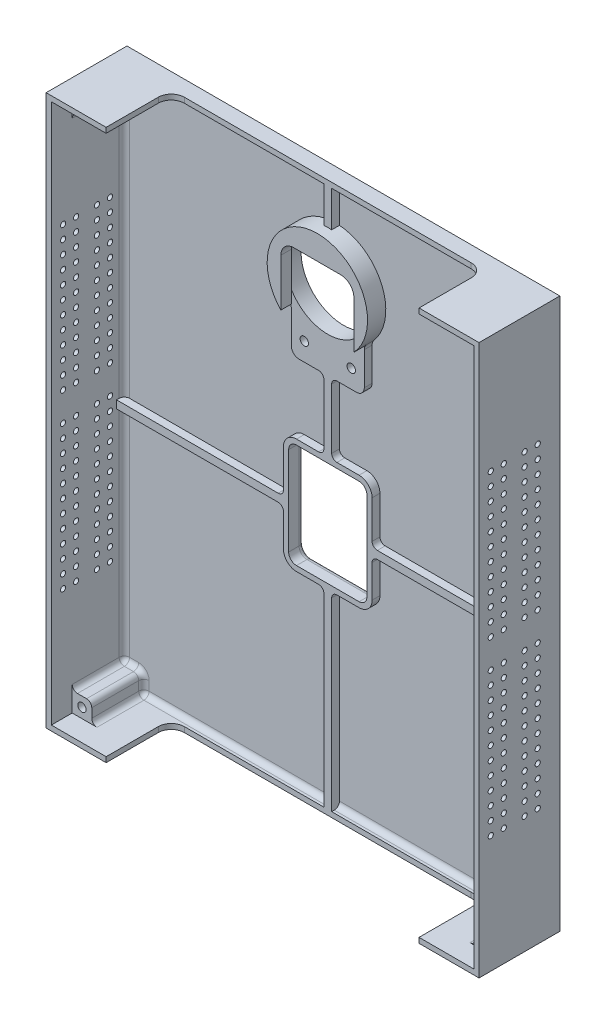
SolidWorks part; units mm, degrees
ref_plane "Front Plane" through (0, 0, 0) normal (0, 0, 1) x (1, 0, 0)
ref_plane "Top Plane" through (0, 0, 0) normal (0, 1, 0) x (1, 0, 0)
ref_plane "Right Plane" through (0, 0, 0) normal (1, 0, 0) x (0, 0, -1)
ref_plane "Plane1" through (0, 0, -1) normal (0, 0, 1) x (1, 0, 0)
sketch "Sketch5" plane through (0, 0, -1) normal (0, 0, 1) x (1, 0, 0)
  line L0 (100, 83.2573) -> (100, -169.2647) construction
  line L2 (17, 83.2573) -> (17, -127.7573)
  line L3 (17, -127.7573) -> (183, -127.7573)
  line L4 (183, 83.2573) -> (183, -127.7573)
  line L5 (17, 83.2573) -> (183, 83.2573)
  circle A0 centre (100, 48.2573) radius 16.25
  point P17 (45, 83.2573)
  dimension "D1" = 166
  dimension "D2" = 83
extrude "Boss-Extrude5" add sketch "Sketch5" along normal blind 3
sketch "Sketch6" plane through (0, 0, 2) normal (0, 0, 1) x (1, 0, 0)
  line L0 (116.25, 48.2573) -> (83.75, 48.2573) construction
  line L2 (86, 35.0451) -> (86, 18.2573)
  line L3 (86, 18.2573) -> (114, 18.2573)
  line L4 (114, 35.0451) -> (114, 18.2573)
  line L5 (100, 48.2573) -> (100, 52.872) construction
  circle A1 centre (100, 48.2573) radius 16.25
  arc A2 (114, 35.0451) -> (86, 35.0451) centre (100, 48.2573) ccw
  circle A6 centre (100, 48.2573) radius 16.25 construction
extrude "Boss-Extrude6" add sketch "Sketch6" along normal blind 3
sketch "Sketch7" plane through (0, 0, 5) normal (0, 0, 1) x (1, 0, 0)
  line L0 (114, 35.0451) -> (114, 53.2573)
  line L1 (109, 58.2573) -> (91, 58.2573)
  line L2 (86, 53.2573) -> (86, 35.0451)
  line L3 (100, 64.5073) -> (100, 48.2573) construction
  line L4 (100, 48.2573) -> (116.25, 48.2573) construction
  arc A4 (91, 58.2573) -> (86, 53.2573) centre (91, 53.2573) ccw
  arc A5 (114, 53.2573) -> (109, 58.2573) centre (109, 53.2573) ccw
  arc A8 (114, 35.0451) -> (86, 35.0451) centre (100, 48.2573) ccw
  circle A9 centre (100, 48.2573) radius 19.25 construction
  circle A10 centre (100, 48.2573) radius 16.25 construction
extrude "Boss-Extrude7" add sketch "Sketch7" along normal blind 4
sketch "Sketch8" plane through (0, 0, 2) normal (0, 0, 1) x (1, 0, 0)
  line L4 (17, -127.7573) -> (183, -127.7573)
  line L5 (183, -127.7573) -> (183, 83.2573)
  line L6 (183, 83.2573) -> (17, 83.2573)
  line L7 (17, 83.2573) -> (17, -127.7573)
  line L8 (17, -127.7573) -> (183, -127.7573)
  line L9 (183, -127.7573) -> (183, 83.2573)
  line L10 (183, 83.2573) -> (17, 83.2573)
  line L11 (17, 83.2573) -> (17, -127.7573)
  line L12 (19, -125.7573) -> (181, -125.7573)
  line L13 (181, -125.7573) -> (181, 81.2573)
  line L14 (181, 81.2573) -> (19, 81.2573)
  line L15 (19, 81.2573) -> (19, -125.7573)
  dimension "D1" = 0
  dimension "D2" = 2
extrude "Boss-Extrude8" add sketch "Sketch8" along normal blind 28
fillet "Fillet2" radius 3 4 edges at (114, 18.2573, 3.5) (114, 35.0451, 3.5) (86, 18.2573, 3.5) (86, 35.0451, 3.5)
sketch "Sketch9" plane through (0, 0, 5) normal (0, 0, 1) x (1, 0, 0)
  line L0 (100, 48.2573) -> (100, 25.2573) construction
  line L1 (91, 25.2573) -> (109, 25.2573) construction
  line L2 (100, 25.2573) -> (100, 23.2329) construction
  circle A0 centre (91, 25.2573) radius 1.6
  circle A1 centre (109, 25.2573) radius 1.6
extrude "Cut-Extrude1" cut sketch "Sketch9" against normal up to surface (6 mm away) up to face at (100, -22.25, -1)
sketch "Sketch12" plane through (183, 0, 0) normal (1, 0, 0) x (0, 0, -1)
  circle A0 centre (-12.5, -16.7427) radius 1
  circle A1 centre (-7.5, -16.7427) radius 1
  circle A2 centre (-7.5, -11.7427) radius 1
  circle A3 centre (-7.5, -6.7427) radius 1
  circle A4 centre (-7.5, -1.7427) radius 1
  circle A5 centre (-7.5, 3.2573) radius 1
  circle A6 centre (-7.5, 8.2573) radius 1
  circle A7 centre (-7.5, 13.2573) radius 1
  circle A8 centre (-7.5, 18.2573) radius 1
  circle A9 centre (-7.5, 23.2573) radius 1
  circle A10 centre (-7.5, 28.2573) radius 1
  circle A11 centre (-7.5, 33.2573) radius 1
  circle A12 centre (-7.5, 38.2573) radius 1
  circle A13 centre (-12.5, -11.7427) radius 1
  circle A14 centre (-12.5, -6.7427) radius 1
  circle A15 centre (-12.5, -1.7427) radius 1
  circle A16 centre (-12.5, 3.2573) radius 1
  circle A17 centre (-12.5, 8.2573) radius 1
  circle A18 centre (-12.5, 13.2573) radius 1
  circle A19 centre (-12.5, 18.2573) radius 1
  circle A20 centre (-12.5, 23.2573) radius 1
  circle A21 centre (-12.5, 28.2573) radius 1
  circle A22 centre (-12.5, 33.2573) radius 1
  circle A23 centre (-12.5, 38.2573) radius 1
  circle A24 centre (-12.5, -82.7573) radius 1
  circle A25 centre (-12.5, -77.7573) radius 1
  circle A26 centre (-12.5, -72.7573) radius 1
  circle A27 centre (-12.5, -67.7573) radius 1
  circle A28 centre (-12.5, -62.7573) radius 1
  circle A29 centre (-12.5, -57.7573) radius 1
  circle A30 centre (-12.5, -52.7573) radius 1
  circle A31 centre (-12.5, -47.7573) radius 1
  circle A32 centre (-12.5, -42.7573) radius 1
  circle A33 centre (-12.5, -37.7573) radius 1
  circle A34 centre (-12.5, -32.7573) radius 1
  circle A35 centre (-7.5, -82.7573) radius 1
  circle A36 centre (-7.5, -77.7573) radius 1
  circle A37 centre (-7.5, -72.7573) radius 1
  circle A38 centre (-7.5, -67.7573) radius 1
  circle A39 centre (-7.5, -62.7573) radius 1
  circle A40 centre (-7.5, -57.7573) radius 1
  circle A41 centre (-7.5, -52.7573) radius 1
  circle A42 centre (-7.5, -47.7573) radius 1
  circle A43 centre (-7.5, -42.7573) radius 1
  circle A44 centre (-7.5, -37.7573) radius 1
  circle A45 centre (-7.5, -32.7573) radius 1
  circle A46 centre (-7.5, -27.7573) radius 1
  circle A47 centre (-12.5, -27.7573) radius 1
  circle A48 centre (-20.5, -27.7573) radius 1
  circle A49 centre (-25.5, -27.7573) radius 1
  circle A50 centre (-25.5, -32.7573) radius 1
  circle A51 centre (-25.5, -37.7573) radius 1
  circle A52 centre (-25.5, -42.7573) radius 1
  circle A53 centre (-25.5, -47.7573) radius 1
  circle A54 centre (-25.5, -52.7573) radius 1
  circle A55 centre (-25.5, -57.7573) radius 1
  circle A56 centre (-25.5, -62.7573) radius 1
  circle A57 centre (-25.5, -67.7573) radius 1
  circle A58 centre (-25.5, -72.7573) radius 1
  circle A59 centre (-25.5, -77.7573) radius 1
  circle A60 centre (-25.5, -82.7573) radius 1
  circle A61 centre (-20.5, -32.7573) radius 1
  circle A62 centre (-20.5, -37.7573) radius 1
  circle A63 centre (-20.5, -42.7573) radius 1
  circle A64 centre (-20.5, -47.7573) radius 1
  circle A65 centre (-20.5, -52.7573) radius 1
  circle A66 centre (-20.5, -57.7573) radius 1
  circle A67 centre (-20.5, -62.7573) radius 1
  circle A68 centre (-20.5, -67.7573) radius 1
  circle A69 centre (-20.5, -72.7573) radius 1
  circle A70 centre (-20.5, -77.7573) radius 1
  circle A71 centre (-20.5, -82.7573) radius 1
  circle A72 centre (-20.5, 38.2573) radius 1
  circle A73 centre (-20.5, 33.2573) radius 1
  circle A74 centre (-20.5, 28.2573) radius 1
  circle A75 centre (-20.5, 23.2573) radius 1
  circle A76 centre (-20.5, 18.2573) radius 1
  circle A77 centre (-20.5, 13.2573) radius 1
  circle A78 centre (-20.5, 8.2573) radius 1
  circle A79 centre (-20.5, 3.2573) radius 1
  circle A80 centre (-20.5, -1.7427) radius 1
  circle A81 centre (-20.5, -6.7427) radius 1
  circle A82 centre (-20.5, -11.7427) radius 1
  circle A83 centre (-25.5, 38.2573) radius 1
  circle A84 centre (-25.5, 33.2573) radius 1
  circle A85 centre (-25.5, 28.2573) radius 1
  circle A86 centre (-25.5, 23.2573) radius 1
  circle A87 centre (-25.5, 18.2573) radius 1
  circle A88 centre (-25.5, 13.2573) radius 1
  circle A89 centre (-25.5, 8.2573) radius 1
  circle A90 centre (-25.5, 3.2573) radius 1
  circle A91 centre (-25.5, -1.7427) radius 1
  circle A92 centre (-25.5, -6.7427) radius 1
  circle A93 centre (-25.5, -11.7427) radius 1
  circle A94 centre (-25.5, -16.7427) radius 1
  circle A95 centre (-20.5, -16.7427) radius 1
  dimension "D1" = 2
  dimension "D2" = 12
extrude "Cut-Extrude4" cut sketch "Sketch12" against normal up to surface (2 mm away) up to face at (181, -22.25, 16)
sketch "Sketch13" plane through (0, 0, -1) normal (0, 0, -1) x (-1, 0, 0)
  line L0 (-183, -30.7808) -> (-100, -30.7808) construction
  line L1 (-183, -127.7573) -> (-183, 83.2573) construction
  line L6 (-100, 83.2573) -> (-100, -30.7808) construction
  line L7 (-183, 83.2573) -> (-17, 83.2573) construction
  line L14 (-85, -47.7808) -> (-85, -13.7808)
  line L15 (-88, -10.7808) -> (-112, -10.7808)
  line L16 (-115, -13.7808) -> (-115, -47.7808)
  line L17 (-112, -50.7808) -> (-88, -50.7808)
  circle A1 centre (-100, -30.7808) radius 9 construction
  arc A15 (-88, -50.7808) -> (-85, -47.7808) centre (-88, -47.7808) ccw
  arc A16 (-85, -13.7808) -> (-88, -10.7808) centre (-88, -13.7808) ccw
  arc A17 (-112, -10.7808) -> (-115, -13.7808) centre (-112, -13.7808) ccw
  arc A18 (-115, -47.7808) -> (-112, -50.7808) centre (-112, -47.7808) ccw
extrude "Cut-Extrude5" cut sketch "Sketch13" against normal blind 3
sketch "Sketch14" plane through (17, 0, 0) normal (-1, 0, 0) x (0, 0, 1)
  circle A1 centre (12.5, -82.7573) radius 1
  circle A2 centre (12.5, -82.7573) radius 1
  circle A3 centre (12.5, -16.7427) radius 1
  circle A4 centre (12.5, -16.7427) radius 1
  circle A5 centre (7.5, 18.2573) radius 1
  circle A6 centre (7.5, 18.2573) radius 1
  circle A7 centre (7.5, 13.2573) radius 1
  circle A8 centre (7.5, 13.2573) radius 1
  circle A9 centre (7.5, 8.2573) radius 1
  circle A10 centre (7.5, 8.2573) radius 1
  circle A11 centre (7.5, 3.2573) radius 1
  circle A12 centre (7.5, 3.2573) radius 1
  circle A13 centre (7.5, -1.7427) radius 1
  circle A14 centre (7.5, -1.7427) radius 1
  circle A15 centre (7.5, -6.7427) radius 1
  circle A16 centre (7.5, -6.7427) radius 1
  circle A17 centre (7.5, -11.7427) radius 1
  circle A18 centre (7.5, -11.7427) radius 1
  circle A19 centre (7.5, -16.7427) radius 1
  circle A20 centre (7.5, -16.7427) radius 1
  circle A21 centre (12.5, 3.2573) radius 1
  circle A22 centre (12.5, 3.2573) radius 1
  circle A23 centre (12.5, -1.7427) radius 1
  circle A24 centre (12.5, -1.7427) radius 1
  circle A25 centre (12.5, -6.7427) radius 1
  circle A26 centre (12.5, -6.7427) radius 1
  circle A27 centre (12.5, -11.7427) radius 1
  circle A28 centre (12.5, -11.7427) radius 1
  circle A29 centre (7.5, 38.2573) radius 1
  circle A30 centre (7.5, 38.2573) radius 1
  circle A31 centre (7.5, 33.2573) radius 1
  circle A32 centre (7.5, 33.2573) radius 1
  circle A33 centre (7.5, 28.2573) radius 1
  circle A34 centre (7.5, 28.2573) radius 1
  circle A35 centre (7.5, 23.2573) radius 1
  circle A36 centre (7.5, 23.2573) radius 1
  circle A37 centre (12.5, -77.7573) radius 1
  circle A38 centre (12.5, -77.7573) radius 1
  circle A39 centre (12.5, 38.2573) radius 1
  circle A40 centre (12.5, 38.2573) radius 1
  circle A41 centre (12.5, 33.2573) radius 1
  circle A42 centre (12.5, 33.2573) radius 1
  circle A43 centre (12.5, 28.2573) radius 1
  circle A44 centre (12.5, 28.2573) radius 1
  circle A45 centre (12.5, 23.2573) radius 1
  circle A46 centre (12.5, 23.2573) radius 1
  circle A47 centre (12.5, 18.2573) radius 1
  circle A48 centre (12.5, 18.2573) radius 1
  circle A49 centre (12.5, 13.2573) radius 1
  circle A50 centre (12.5, 13.2573) radius 1
  circle A51 centre (12.5, 8.2573) radius 1
  circle A52 centre (12.5, 8.2573) radius 1
  circle A53 centre (12.5, -37.7573) radius 1
  circle A54 centre (12.5, -37.7573) radius 1
  circle A55 centre (12.5, -42.7573) radius 1
  circle A56 centre (12.5, -42.7573) radius 1
  circle A57 centre (12.5, -47.7573) radius 1
  circle A58 centre (12.5, -47.7573) radius 1
  circle A59 centre (12.5, -52.7573) radius 1
  circle A60 centre (12.5, -52.7573) radius 1
  circle A61 centre (12.5, -57.7573) radius 1
  circle A62 centre (12.5, -57.7573) radius 1
  circle A63 centre (12.5, -62.7573) radius 1
  circle A64 centre (12.5, -62.7573) radius 1
  circle A65 centre (12.5, -67.7573) radius 1
  circle A66 centre (12.5, -67.7573) radius 1
  circle A67 centre (12.5, -72.7573) radius 1
  circle A68 centre (12.5, -72.7573) radius 1
  circle A69 centre (7.5, -52.7573) radius 1
  circle A70 centre (7.5, -52.7573) radius 1
  circle A71 centre (7.5, -57.7573) radius 1
  circle A72 centre (7.5, -57.7573) radius 1
  circle A73 centre (7.5, -62.7573) radius 1
  circle A74 centre (7.5, -62.7573) radius 1
  circle A75 centre (7.5, -67.7573) radius 1
  circle A76 centre (7.5, -67.7573) radius 1
  circle A77 centre (7.5, -72.7573) radius 1
  circle A78 centre (7.5, -72.7573) radius 1
  circle A79 centre (7.5, -77.7573) radius 1
  circle A80 centre (7.5, -77.7573) radius 1
  circle A81 centre (7.5, -82.7573) radius 1
  circle A82 centre (7.5, -82.7573) radius 1
  circle A83 centre (12.5, -32.7573) radius 1
  circle A84 centre (12.5, -32.7573) radius 1
  circle A85 centre (25.5, -27.7573) radius 1
  circle A86 centre (25.5, -27.7573) radius 1
  circle A87 centre (20.5, -27.7573) radius 1
  circle A88 centre (20.5, -27.7573) radius 1
  circle A89 centre (12.5, -27.7573) radius 1
  circle A90 centre (12.5, -27.7573) radius 1
  circle A91 centre (7.5, -27.7573) radius 1
  circle A92 centre (7.5, -27.7573) radius 1
  circle A93 centre (7.5, -32.7573) radius 1
  circle A94 centre (7.5, -32.7573) radius 1
  circle A95 centre (7.5, -37.7573) radius 1
  circle A96 centre (7.5, -37.7573) radius 1
  circle A97 centre (7.5, -42.7573) radius 1
  circle A98 centre (7.5, -42.7573) radius 1
  circle A99 centre (7.5, -47.7573) radius 1
  circle A100 centre (7.5, -47.7573) radius 1
  circle A101 centre (25.5, -67.7573) radius 1
  circle A102 centre (25.5, -67.7573) radius 1
  circle A103 centre (25.5, -62.7573) radius 1
  circle A104 centre (25.5, -62.7573) radius 1
  circle A105 centre (25.5, -57.7573) radius 1
  circle A106 centre (25.5, -57.7573) radius 1
  circle A107 centre (25.5, -52.7573) radius 1
  circle A108 centre (25.5, -52.7573) radius 1
  circle A109 centre (25.5, -47.7573) radius 1
  circle A110 centre (25.5, -47.7573) radius 1
  circle A111 centre (25.5, -42.7573) radius 1
  circle A112 centre (25.5, -42.7573) radius 1
  circle A113 centre (25.5, -37.7573) radius 1
  circle A114 centre (25.5, -37.7573) radius 1
  circle A115 centre (25.5, -32.7573) radius 1
  circle A116 centre (25.5, -32.7573) radius 1
  circle A117 centre (20.5, -52.7573) radius 1
  circle A118 centre (20.5, -52.7573) radius 1
  circle A119 centre (20.5, -47.7573) radius 1
  circle A120 centre (20.5, -47.7573) radius 1
  circle A121 centre (20.5, -42.7573) radius 1
  circle A122 centre (20.5, -42.7573) radius 1
  circle A123 centre (20.5, -37.7573) radius 1
  circle A124 centre (20.5, -37.7573) radius 1
  circle A125 centre (20.5, -32.7573) radius 1
  circle A126 centre (20.5, -32.7573) radius 1
  circle A127 centre (25.5, -82.7573) radius 1
  circle A128 centre (25.5, -82.7573) radius 1
  circle A129 centre (25.5, -77.7573) radius 1
  circle A130 centre (25.5, -77.7573) radius 1
  circle A131 centre (25.5, -72.7573) radius 1
  circle A132 centre (25.5, -72.7573) radius 1
  circle A133 centre (20.5, 33.2573) radius 1
  circle A134 centre (20.5, 33.2573) radius 1
  circle A135 centre (20.5, 38.2573) radius 1
  circle A136 centre (20.5, 38.2573) radius 1
  circle A137 centre (20.5, -82.7573) radius 1
  circle A138 centre (20.5, -82.7573) radius 1
  circle A139 centre (20.5, -77.7573) radius 1
  circle A140 centre (20.5, -77.7573) radius 1
  circle A141 centre (20.5, -72.7573) radius 1
  circle A142 centre (20.5, -72.7573) radius 1
  circle A143 centre (20.5, -67.7573) radius 1
  circle A144 centre (20.5, -67.7573) radius 1
  circle A145 centre (20.5, -62.7573) radius 1
  circle A146 centre (20.5, -62.7573) radius 1
  circle A147 centre (20.5, -57.7573) radius 1
  circle A148 centre (20.5, -57.7573) radius 1
  circle A149 centre (20.5, -6.7427) radius 1
  circle A150 centre (20.5, -6.7427) radius 1
  circle A151 centre (20.5, -1.7427) radius 1
  circle A152 centre (20.5, -1.7427) radius 1
  circle A153 centre (20.5, 3.2573) radius 1
  circle A154 centre (20.5, 3.2573) radius 1
  circle A155 centre (20.5, 8.2573) radius 1
  circle A156 centre (20.5, 8.2573) radius 1
  circle A157 centre (20.5, 13.2573) radius 1
  circle A158 centre (20.5, 13.2573) radius 1
  circle A159 centre (20.5, 18.2573) radius 1
  circle A160 centre (20.5, 18.2573) radius 1
  circle A161 centre (20.5, 23.2573) radius 1
  circle A162 centre (20.5, 23.2573) radius 1
  circle A163 centre (20.5, 28.2573) radius 1
  circle A164 centre (20.5, 28.2573) radius 1
  circle A165 centre (25.5, 8.2573) radius 1
  circle A166 centre (25.5, 8.2573) radius 1
  circle A167 centre (25.5, 13.2573) radius 1
  circle A168 centre (25.5, 13.2573) radius 1
  circle A169 centre (25.5, 18.2573) radius 1
  circle A170 centre (25.5, 18.2573) radius 1
  circle A171 centre (25.5, 23.2573) radius 1
  circle A172 centre (25.5, 23.2573) radius 1
  circle A173 centre (25.5, 28.2573) radius 1
  circle A174 centre (25.5, 28.2573) radius 1
  circle A175 centre (25.5, 33.2573) radius 1
  circle A176 centre (25.5, 33.2573) radius 1
  circle A177 centre (25.5, 38.2573) radius 1
  circle A178 centre (25.5, 38.2573) radius 1
  circle A179 centre (20.5, -11.7427) radius 1
  circle A180 centre (20.5, -11.7427) radius 1
  circle A181 centre (20.5, -16.7427) radius 1
  circle A182 centre (20.5, -16.7427) radius 1
  circle A183 centre (25.5, -16.7427) radius 1
  circle A184 centre (25.5, -16.7427) radius 1
  circle A185 centre (25.5, -11.7427) radius 1
  circle A186 centre (25.5, -11.7427) radius 1
  circle A187 centre (25.5, -6.7427) radius 1
  circle A188 centre (25.5, -6.7427) radius 1
  circle A189 centre (25.5, -1.7427) radius 1
  circle A190 centre (25.5, -1.7427) radius 1
  circle A191 centre (25.5, 3.2573) radius 1
  circle A192 centre (25.5, 3.2573) radius 1
  dimension "D1" = 0
  dimension "D2" = 0
  dimension "D3" = 0
  dimension "D4" = 0
  dimension "D5" = 0
  dimension "D6" = 0
  dimension "D7" = 0
  dimension "D8" = 0
  dimension "D9" = 0
  dimension "D10" = 0
  dimension "D11" = 0
  dimension "D12" = 0
  dimension "D13" = 0
  dimension "D14" = 0
  dimension "D15" = 0
  dimension "D16" = 0
  dimension "D17" = 0
  dimension "D18" = 0
  dimension "D19" = 0
  dimension "D20" = 0
  dimension "D21" = 0
  dimension "D22" = 0
  dimension "D23" = 0
  dimension "D24" = 0
  dimension "D25" = 0
  dimension "D26" = 0
  dimension "D27" = 0
  dimension "D28" = 0
  dimension "D29" = 0
  dimension "D30" = 0
  dimension "D31" = 0
  dimension "D32" = 0
  dimension "D33" = 0
  dimension "D34" = 0
  dimension "D35" = 0
  dimension "D36" = 0
  dimension "D37" = 0
  dimension "D38" = 0
  dimension "D39" = 0
  dimension "D40" = 0
  dimension "D41" = 0
  dimension "D42" = 0
  dimension "D43" = 0
  dimension "D44" = 0
  dimension "D45" = 0
  dimension "D46" = 0
  dimension "D47" = 0
  dimension "D48" = 0
  dimension "D49" = 0
  dimension "D50" = 0
  dimension "D51" = 0
  dimension "D52" = 0
  dimension "D53" = 0
  dimension "D54" = 0
  dimension "D55" = 0
  dimension "D56" = 0
  dimension "D57" = 0
  dimension "D58" = 0
  dimension "D59" = 0
  dimension "D60" = 0
  dimension "D61" = 0
  dimension "D62" = 0
  dimension "D63" = 0
  dimension "D64" = 0
  dimension "D65" = 0
  dimension "D66" = 0
  dimension "D67" = 0
  dimension "D68" = 0
  dimension "D69" = 0
  dimension "D70" = 0
  dimension "D71" = 0
  dimension "D72" = 0
  dimension "D73" = 0
  dimension "D74" = 0
  dimension "D75" = 0
  dimension "D76" = 0
  dimension "D77" = 0
  dimension "D78" = 0
  dimension "D79" = 0
  dimension "D80" = 0
  dimension "D81" = 0
  dimension "D82" = 0
  dimension "D83" = 0
  dimension "D84" = 0
  dimension "D85" = 0
  dimension "D86" = 0
  dimension "D87" = 0
  dimension "D88" = 0
  dimension "D89" = 0
  dimension "D90" = 0
  dimension "D91" = 0
  dimension "D92" = 0
  dimension "D93" = 0
  dimension "D94" = 0
  dimension "D95" = 0
  dimension "D96" = 0
extrude "Cut-Extrude6" cut sketch "Sketch14" against normal up to surface (2 mm away) up to face at (19, -22.25, 16)
sketch "Sketch15" plane through (0, -127.7573, 0) normal (0, -1, 0) x (1, 0, 0)
  line L5 (100, -1) -> (100, 30) construction
  line L6 (17, -1) -> (183, -1) construction
  line L7 (17, 30) -> (183, 30) construction
  line L8 (40, 30) -> (160, 30)
  line L9 (40, 30) -> (40, 10)
  line L10 (45, 5) -> (155, 5)
  line L11 (160, 30) -> (160, 10)
  arc A4 (155, 5) -> (160, 10) centre (155, 10) ccw
  arc A5 (40, 10) -> (45, 5) centre (45, 10) ccw
  point P12 (160, 5)
  point P15 (40, 5)
  dimension "D4" = 5
  dimension "D1" = 60
  dimension "D2" = 120
  dimension "D3" = 25
extrude "Cut-Extrude7" cut sketch "Sketch15" against normal up to surface (2 mm away) up to face at (100, -125.7573, 16)
sketch "Sketch16" plane through (0, 83.2573, 0) normal (0, 1, 0) x (1, 0, 0)
  line L4 (40, -30) -> (160, -30)
  line L5 (40, -30) -> (160, -30)
  line L6 (160, -30) -> (160, -10)
  line L7 (160, -30) -> (160, -10)
  line L12 (155, -5) -> (45, -5)
  line L13 (155, -5) -> (45, -5)
  line L14 (40, -10) -> (40, -30)
  line L15 (40, -10) -> (40, -30)
  arc A2 (160, -10) -> (155, -5) centre (155, -10) ccw
  arc A3 (160, -10) -> (155, -5) centre (155, -10) ccw
  arc A4 (45, -5) -> (40, -10) centre (45, -10) ccw
  arc A5 (45, -5) -> (40, -10) centre (45, -10) ccw
  dimension "D1" = 0
extrude "Cut-Extrude8" cut sketch "Sketch16" against normal up to surface (2 mm away) up to face at (100, 81.2573, 16)
sketch "Sketch18" plane through (0, 0, 2) normal (0, 0, 1) x (1, 0, 0)
  line L1 (19, -125.7573) -> (26.5, -125.7573)
  line L2 (19, -125.7573) -> (19, -118.2573)
  line L3 (19, -118.2573) -> (26.5, -118.2573)
  line L4 (26.5, -125.7573) -> (26.5, -118.2573)
  line L5 (181, -125.7573) -> (173.5, -125.7573)
  line L6 (181, -125.7573) -> (181, -118.2573)
  line L7 (181, -118.2573) -> (173.5, -118.2573)
  line L8 (173.5, -125.7573) -> (173.5, -118.2573)
  line L9 (19, 81.2573) -> (26.5, 81.2573)
  line L10 (19, 81.2573) -> (19, 73.7573)
  line L11 (19, 73.7573) -> (26.5, 73.7573)
  line L12 (26.5, 81.2573) -> (26.5, 73.7573)
  line L13 (181, 81.2573) -> (173.5, 81.2573)
  line L14 (181, 81.2573) -> (181, 73.7573)
  line L15 (181, 73.7573) -> (173.5, 73.7573)
  line L16 (173.5, 81.2573) -> (173.5, 73.7573)
extrude "Boss-Extrude10" add sketch "Sketch18" along normal blind 20
fillet "Fillet3" radius 2 12 edges at (181, 73.7573, 12) (173.5, 73.7573, 12) (173.5, 81.2573, 12) (26.5, 81.2573, 12) (26.5, 73.7573, 12) (19, 73.7573, 12) (19, -118.2573, 12) (26.5, -118.2573, 12) (26.5, -125.7573, 12) (181, -118.2573, 12) (173.5, -118.2573, 12) (173.5, -125.7573, 12)
sketch "Sketch19" plane through (0, 0, 22) normal (0, 0, 1) x (1, 0, 0)
  line L4 (100, -127.7573) -> (100, 83.2573) construction
  line L5 (45, -127.7573) -> (155, -127.7573) construction
  line L6 (155, 83.2573) -> (45, 83.2573) construction
  line L7 (100, -22.25) -> (17, -22.25) construction
  line L8 (17, 83.2573) -> (17, -127.7573) construction
  circle A0 centre (22.75, -122.0073) radius 1.6
  circle A1 centre (177.25, -122.0073) radius 1.6
  circle A2 centre (177.25, 77.5073) radius 1.6
  circle A3 centre (22.75, 77.5073) radius 1.6
extrude "Cut-Extrude9" cut sketch "Sketch19" against normal up to surface (23 mm away) up to face at (100, -30.7808, -1)
fillet "Fillet4" radius 2 24 edges at (180.4142, -117.6715, 2) (177.25, -118.2573, 2) (174.0858, -118.8431, 2) (173.5, -122.0073, 2) (172.9142, -125.1715, 2) (100, -125.7573, 2) (27.0858, -125.1715, 2) (26.5, -122.0073, 2) (25.9142, -118.8431, 2) (22.75, -118.2573, 2) (19.5858, -117.6715, 2) (19, -22.25, 2) (19.5858, 73.1715, 2) (22.75, 73.7573, 2) (25.9142, 74.3431, 2) (26.5, 77.5073, 2) (27.0858, 80.6715, 2) (100, 81.2573, 2) (172.9142, 80.6715, 2) (173.5, 77.5073, 2) (174.0858, 74.3431, 2) (177.25, 73.7573, 2) (180.4142, 73.1715, 2) (181, -22.25, 2)
sketch "Sketch20" plane through (0, 0, 2) normal (0, 0, 1) x (1, 0, 0)
  line L0 (83, -30.2573) -> (83, -13.7808)
  line L1 (155, 83.2573) -> (45, 83.2573) construction
  line L2 (45, -127.7573) -> (155, -127.7573) construction
  line L3 (88, -10.7808) -> (112, -10.7808) construction
  line L4 (101.5, -127.7573) -> (98.5, -127.7573)
  line L5 (101.5, -127.7573) -> (101.5, -52.7808)
  line L6 (101.5, 83.2573) -> (98.5, 83.2573)
  line L7 (98.5, -127.7573) -> (98.5, -52.7808)
  line L8 (115, -13.7808) -> (115, -47.7808) construction
  line L9 (112, -50.7808) -> (88, -50.7808) construction
  line L10 (85, -47.7808) -> (85, -13.7808) construction
  line L11 (88, -10.7808) -> (112, -10.7808)
  line L12 (115, -13.7808) -> (115, -47.7808)
  line L13 (112, -50.7808) -> (88, -50.7808)
  line L14 (85, -47.7808) -> (85, -13.7808)
  line L15 (88, -8.7808) -> (98.5, -8.7808)
  line L16 (117, -13.7808) -> (117, -30.2573)
  line L17 (112, -52.7808) -> (101.5, -52.7808)
  line L18 (83, -47.7808) -> (83, -33.2573)
  line L19 (101.5, -8.7808) -> (112, -8.7808)
  line L20 (183, -127.7573) -> (183, 83.2573) construction
  line L21 (183, -33.2573) -> (117, -33.2573)
  line L22 (183, -33.2573) -> (183, -30.2573)
  line L23 (183, -30.2573) -> (117, -30.2573)
  line L24 (17, -33.2573) -> (17, -30.2573)
  line L25 (17, 83.2573) -> (17, -127.7573) construction
  line L26 (83, -33.2573) -> (17, -33.2573)
  line L28 (98.5, -52.7808) -> (88, -52.7808)
  line L31 (83, -30.2573) -> (17, -30.2573)
  line L32 (98.5, -8.7808) -> (98.5, 18.2573)
  line L33 (112, -52.7808) -> (88, -52.7808) construction
  line L35 (117, -33.2573) -> (117, -47.7808)
  line L37 (101.5, -8.7808) -> (101.5, 18.2573)
  line L38 (117, -13.7808) -> (117, -47.7808) construction
  line L39 (88, -8.7808) -> (112, -8.7808) construction
  line L40 (83, -47.7808) -> (83, -13.7808) construction
  line L42 (89, 18.2573) -> (111, 18.2573) construction
  line L43 (98.5, 18.2573) -> (101.5, 18.2573)
  line L44 (98.5, 64.4379) -> (98.5, 83.2573)
  line L45 (101.5, 64.4379) -> (101.5, 83.2573)
  line L49 (114, 53.2573) -> (114, 40.0073)
  line L50 (91, 58.2573) -> (109, 58.2573)
  line L51 (86, 40.0073) -> (86, 53.2573)
  arc A0 (88, -10.7808) -> (85, -13.7808) centre (88, -13.7808) ccw construction
  arc A1 (115, -13.7808) -> (112, -10.7808) centre (112, -13.7808) ccw construction
  arc A2 (112, -50.7808) -> (115, -47.7808) centre (112, -47.7808) ccw construction
  arc A3 (85, -47.7808) -> (88, -50.7808) centre (88, -47.7808) ccw construction
  arc A4 (88, -10.7808) -> (85, -13.7808) centre (88, -13.7808) ccw
  arc A5 (115, -13.7808) -> (112, -10.7808) centre (112, -13.7808) ccw
  arc A6 (112, -50.7808) -> (115, -47.7808) centre (112, -47.7808) ccw
  arc A7 (85, -47.7808) -> (88, -50.7808) centre (88, -47.7808) ccw
  arc A8 (117, -13.7808) -> (112, -8.7808) centre (112, -13.7808) ccw
  arc A9 (112, -52.7808) -> (117, -47.7808) centre (112, -47.7808) ccw
  arc A10 (83, -47.7808) -> (88, -52.7808) centre (88, -47.7808) ccw
  arc A11 (88, -8.7808) -> (83, -13.7808) centre (88, -13.7808) ccw
  arc A15 (114, 40.0073) -> (86, 40.0073) centre (100, 48.2573) ccw
  arc A16 (114, 53.2573) -> (109, 58.2573) centre (109, 53.2573) ccw
  arc A17 (91, 58.2573) -> (86, 53.2573) centre (91, 53.2573) ccw
  arc A18 (101.5, 64.4379) -> (98.5, 64.4379) centre (100, 48.2573) ccw
  dimension "D1" = 0
  dimension "D3" = 2
extrude "Boss-Extrude11" add sketch "Sketch20" along normal blind 3
fillet "Fillet5" radius 2 10 edges at (98.5, -52.7808, 3.5) (101.5, -52.7808, 3.5) (117, -33.2573, 3.5) (117, -30.2573, 3.5) (83, -33.2573, 3.5) (83, -30.2573, 3.5) (98.5, -8.7808, 3.5) (101.5, -8.7808, 3.5) (98.5, 18.2573, 3.5) (101.5, 18.2573, 3.5)
sketch "Sketch21" plane through (0, 0, -1) normal (0, 0, -1) x (-1, 0, 0)
  circle A0 centre (-109, 25.2573) radius 2.25
  circle A1 centre (-91, 25.2573) radius 2.25
extrude "Cut-Extrude10" cut sketch "Sketch21" against normal blind 3
fillet "Fillet6" radius 2 8 edges at (85.8787, -49.9021, -1) (100, -50.7808, -1) (114.1213, -49.9021, -1) (115, -30.7808, -1) (114.1213, -11.6594, -1) (100, -10.7808, -1) (85.8787, -11.6594, -1) (85, -30.7808, -1)
